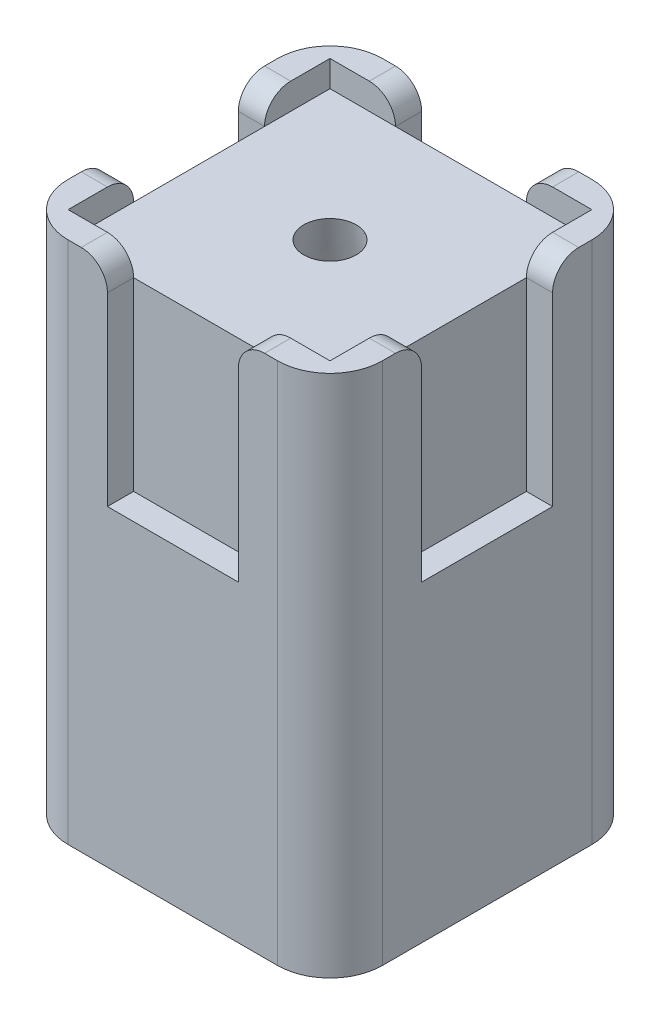
SolidWorks part; units mm, degrees
ref_plane "Front Plane" through (0, 0, 0) normal (0, 0, 1) x (1, 0, 0)
ref_plane "Top Plane" through (0, 0, 0) normal (0, 1, 0) x (1, 0, 0)
ref_plane "Right Plane" through (0, 0, 0) normal (1, 0, 0) x (0, 0, -1)
sketch "Sketch2" plane through (0, 0, 0) normal (0, 1, 0) x (1, 0, 0)
  line L1 (-15, -15) -> (15, -15)
  line L2 (-15, -15) -> (-15, 15)
  line L3 (-15, 15) -> (15, 15)
  line L4 (15, -15) -> (15, 15)
  line L5 (0, 15) -> (0, -15) construction
  line L6 (-15, 0) -> (15, 0) construction
  point P0 (0, 0)
  dimension "D1" = 30
  dimension "D2" = 30
extrude "Boss-Extrude1" add sketch "Sketch2" along normal blind 50
sketch "Sketch3" plane through (0, 50, 0) normal (0, 1, 0) x (1, 0, 0)
  line L1 (-12.5, -12.5) -> (12.5, -12.5)
  line L2 (-12.5, -12.5) -> (-12.5, 12.5)
  line L3 (-12.5, 12.5) -> (12.5, 12.5)
  line L4 (12.5, -12.5) -> (12.5, 12.5)
  line L5 (0, 12.5) -> (0, -12.5) construction
  line L6 (-12.5, 0) -> (12.5, 0) construction
  point P0 (0, 0)
  dimension "D1" = 25
  dimension "D2" = 25
extrude "Cut-Extrude1" cut sketch "Sketch3" against normal blind 2.5
fillet "Fillet1" radius 5 4 edges at (15, 25, 15) (15, 25, -15) (-15, 25, -15) (-15, 25, 15)
sketch "Sketch6" plane through (0, 0, 0) normal (0, -1, 0) x (1, 0, 0)
  circle A0 centre (0, 0) radius 12.5
  dimension "D1" = 25
sketch "Sketch8" plane through (0, 47.5, 0) normal (0, 1, 0) x (1, 0, 0)
  circle A0 centre (0, 0) radius 2.5
  dimension "D1" = 5
loft "Cut-Loft2" cut profiles "Sketch6", "Sketch8" connector at (0, 0, -12.5) connector at (0.7845, 47.5, -2.3737)
sketch "Sketch9" plane through (0, 0, 15) normal (0, 0, 1) x (1, 0, 0)
  line L0 (-10, 50) -> (10, 50) construction
  line L1 (-6.25, 29.8275) -> (6.25, 29.8275)
  line L2 (-6.25, 29.8275) -> (-6.25, 50)
  line L3 (-6.25, 50) -> (6.25, 50)
  line L4 (6.25, 29.8275) -> (6.25, 50)
  line L5 (0, 50) -> (0, 29.8275) construction
  line L6 (-6.25, 39.9138) -> (6.25, 39.9138) construction
  point P0 (0, 39.9138)
  dimension "D1" = 12.5
extrude "Cut-Extrude2" cut sketch "Sketch9" against normal blind 2.5
pattern_circular "CirPattern1" count 4 over 360 about axis through (0, 47.5, 0) along (0, 1, 0) of "Cut-Extrude2", "Cut-Loft2"
fillet "Fillet2" radius 2.5 8 edges at (13.75, 50, 6.25) (13.75, 50, -6.25) (6.25, 50, -13.75) (-6.25, 50, -13.75) (-13.75, 50, -6.25) (-13.75, 50, 6.25) (-6.25, 50, 13.75) (6.25, 50, 13.75)
